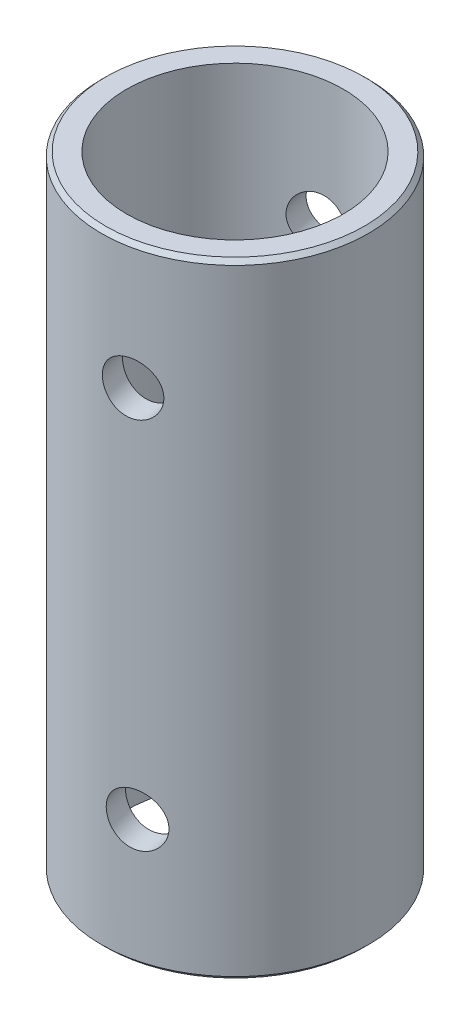
SolidWorks part; units mm, degrees
ref_plane "Front Plane" through (0, 0, 0) normal (0, 0, 1) x (1, 0, 0)
ref_plane "Top Plane" through (0, 0, 0) normal (0, 1, 0) x (1, 0, 0)
ref_plane "Right Plane" through (0, 0, 0) normal (1, 0, 0) x (0, 0, -1)
sketch "Sketch1" plane through (0, 0, 0) normal (0, 1, 0) x (1, 0, 0)
  circle A0 centre (0, 0) radius 7.94
  circle A1 centre (0, 0) radius 6.44
  dimension "D1" = 15.88
  dimension "D2" = 1.5
extrude "Boss-Extrude1" add sketch "Sketch1" along normal blind 37.13
chamfer "Chamfer1" distance 0.25 angle 45 2 edges at (0, 0, 7.94) (0, 37.13, 7.94)
sketch "Sketch2" plane through (-1.3416, 0, -5.6941) normal (-0.2293, 0, -0.9733) x (-0.9733, 0, 0.2293)
  circle A0 centre (0, 7.5) radius 1.55 construction
  circle A1 centre (0, 7.5) radius 1.55
extrude "Cut-Extrude1" cut sketch "Sketch2" against normal through all both and the other way through all
sketch "Sketch3" plane through (-1.1783, 0, -5.7301) normal (-0.2014, 0, -0.9795) x (-0.9795, 0, 0.2014)
  circle A0 centre (0, 29.63) radius 1.55 construction
  circle A1 centre (0, 29.63) radius 1.55
extrude "Cut-Extrude2" cut sketch "Sketch3" against normal through all both and the other way through all
